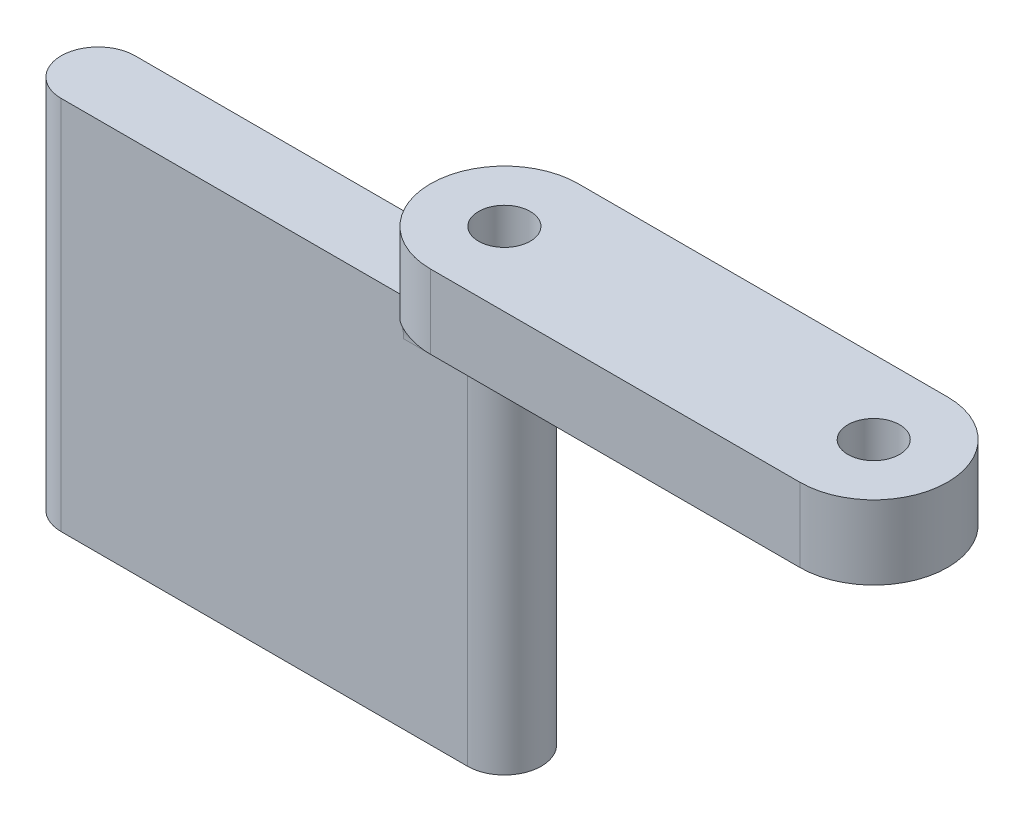
SolidWorks part; units mm, degrees
ref_plane "Front Plane" through (0, 0, 0) normal (0, 0, 1) x (1, 0, 0)
ref_plane "Top Plane" through (0, 0, 0) normal (0, 1, 0) x (1, 0, 0)
ref_plane "Right Plane" through (0, 0, 0) normal (1, 0, 0) x (0, 0, -1)
sketch "Sketch1" plane through (0, 0, 0) normal (0, 1, 0) x (1, 0, 0)
  line L0 (-25, 0) -> (25, 0) construction
  line L1 (-25, 10) -> (25, 10)
  line L2 (-25, -10) -> (25, -10)
  arc A0 (-25, 10) -> (-25, -10) centre (-25, 0) ccw
  arc A1 (25, -10) -> (25, 10) centre (25, 0) ccw
  circle A2 centre (-25, 0) radius 3.5
  circle A3 centre (25, 0) radius 3.5
  point P2 (0, 0)
  dimension "D3" = 7
  dimension "D4" = 7
  dimension "D1" = 20
  dimension "D2" = 50
extrude "Boss-Extrude1" add sketch "Sketch1" along normal blind 10 contours A2 | A3 | L2 A1 L1 A0 region at (-25, 0, 0) region at (25, 0, 0)
sketch "Sketch2" plane through (0, 0, 0) normal (0, -1, 0) x (1, 0, 0)
  line L0 (-25, 0) -> (-80, 0) construction
  line L1 (-25, -5) -> (-80, -5)
  line L2 (-25, 5) -> (-80, 5)
  arc A0 (-25, -5) -> (-25, 5) centre (-25, 0) ccw
  arc A1 (-80, 5) -> (-80, -5) centre (-80, 0) ccw
  point P4 (-52.5, 0)
  dimension "D1" = 55
  dimension "D2" = 10
extrude "Boss-Extrude2" add sketch "Sketch2" along normal blind 50.8
fillet "Fillet1" radius 5 3 edges at (-20, 0, 0) (-29.3301, 0, -5) (-29.3301, 0, 5)
